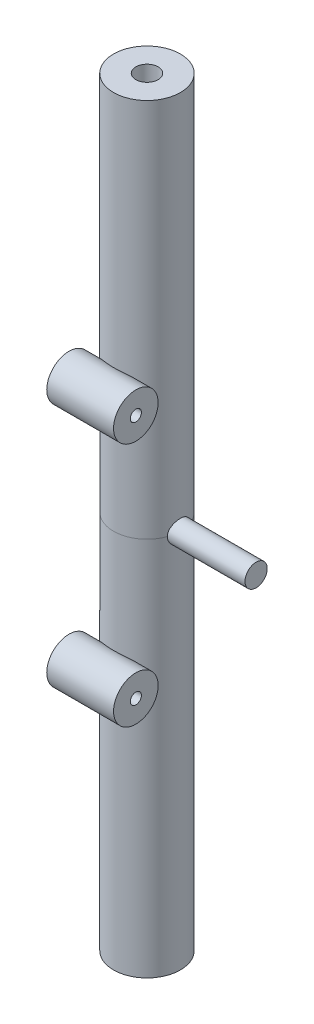
SolidWorks part; units mm, degrees
ref_plane "Płaszczyzna przednia" through (0, 0, 0) normal (0, 0, 1) x (1, 0, 0)
ref_plane "Płaszczyzna górna" through (0, 0, 0) normal (0, 1, 0) x (1, 0, 0)
ref_plane "Płaszczyzna prawa" through (0, 0, 0) normal (1, 0, 0) x (0, 0, -1)
sketch "Szkic1" plane through (0, 0, 0) normal (0, 0, 1) x (1, 0, 0)
  line L0 (10, 0) -> (10, 37.902) construction
  line L1 (0, -123.8759) -> (-20, -123.8759)
  line L2 (0, -123.8759) -> (0, 558.4641)
  line L3 (0, 558.4641) -> (-20, 558.4641)
  line L4 (-20, -123.8759) -> (-20, 558.4641)
  dimension "D1" = 20
  dimension "D2" = 682.34
  dimension "D3" = 10
revolve "Obrót1" add sketch "Szkic1" angle 360 about L0
sketch "Szkic2" plane through (0, 0, 0) normal (0, 0, 1) x (1, 0, 0)
  line L0 (-112.0056, 217.2941) -> (127.5297, 217.2941)
  line L1 (0, -123.8759) -> (0, 558.4641) construction
  point P4 (0, 0)
  point P10 (0, 217.2941)
split line "Linia podziałowa1"
ref_plane "Płaszczyzna1" through (0, 0, 40) normal (0, 0, 1) x (1, 0, 0)
ref_axis "Oś1" through (10, 225.4951, 0) along (0, -1, 0)
sketch "Szkic3" plane through (0, 0, 40) normal (0, 0, 1) x (1, 0, 0)
  line L1 (20, 357.2941) -> (0, 357.2941)
  line L2 (20, 357.2941) -> (20, 297.2941)
  line L3 (20, 297.2941) -> (0, 297.2941)
  line L4 (0, 357.2941) -> (0, 297.2941)
  line L5 (20, 137.2941) -> (0, 137.2941)
  line L6 (20, 137.2941) -> (20, 77.2941)
  line L7 (20, 77.2941) -> (0, 77.2941)
  line L8 (0, 137.2941) -> (0, 77.2941)
  line L9 (10, 225.4951) -> (10, -141.5049) construction
  line L10 (40, 217.2941) -> (-20, 217.2941) construction
  dimension "D1" = 60
  dimension "D2" = 20
  dimension "D3" = 10
  dimension "D4" = 80
  dimension "D5" = 80
sketch "Szkic4" plane through (0, 0, 40) normal (0, 0, 1) x (1, 0, 0)
  line L0 (0, 107.2941) -> (78.1208, 107.2941) construction
  line L1 (-20, 102.2941) -> (40, 102.2941)
  line L2 (-20, 102.2941) -> (-20, 87.2941)
  line L3 (-20, 87.2941) -> (40, 87.2941)
  line L4 (40, 102.2941) -> (40, 87.2941)
  line L5 (20, 137.2941) -> (0, 137.2941) construction
  line L6 (20, 77.2941) -> (0, 77.2941) construction
  line L8 (10, 225.4951) -> (10, -141.5049) construction
  dimension "D1" = 5
  dimension "D2" = 20
  dimension "D3" = 60
  dimension "D4" = 30
revolve "Obrót2" add sketch "Szkic4" angle 360 about L0
ref_plane "Płaszczyzna2" through (0, 217.2941, 0) normal (0, -1, 0) x (-1, 0, 0)
mirror "Lustro1" about plane through (0, 217.2941, 0) normal (0, -1, 0) of "Obrót2"
sketch "Szkic5" plane through (0, 0, 0) normal (1, 0, 0) x (0, 0, -1)
  line L0 (-33, 217.2941) -> (33, 217.2941) construction
  circle A0 centre (0, 217.2941) radius 10
  point P2 (0, 0)
  point P3 (0, 0)
  dimension "D1" = 20
extrude "Dodanie-wyciągnięcie1" add sketch "Szkic5" along normal blind 108 separate body
